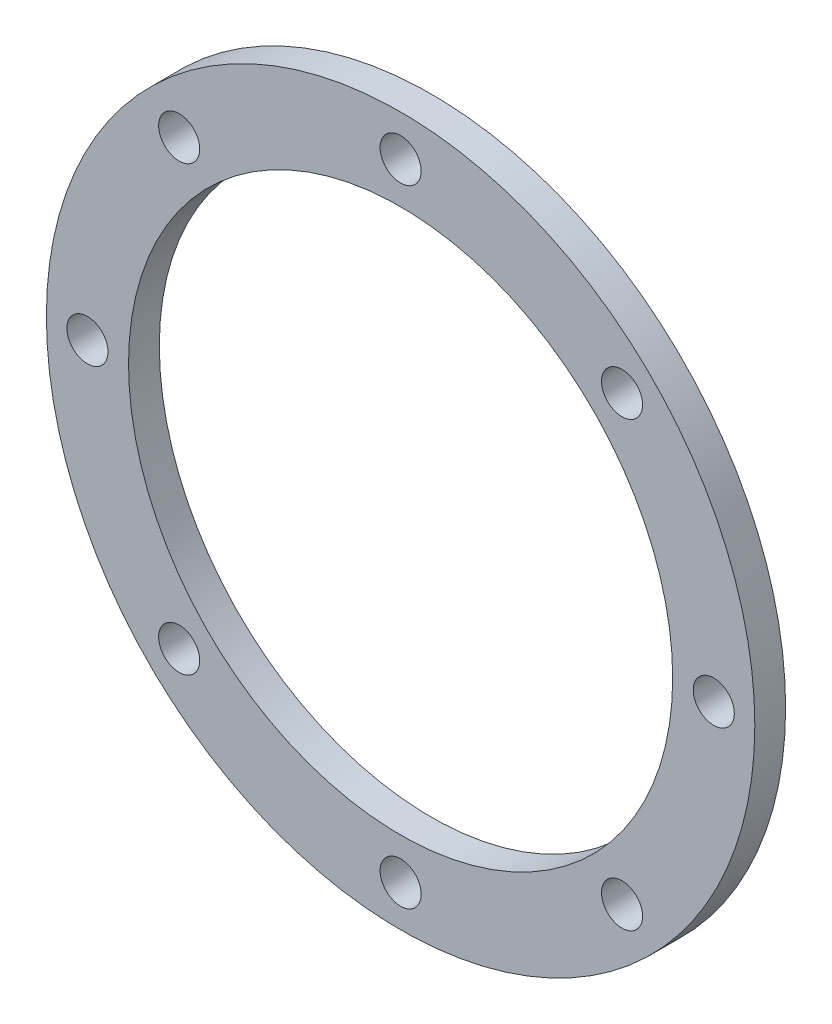
SolidWorks part; units mm, degrees
ref_plane "Front Plane" through (0, 0, 0) normal (0, 0, 1) x (1, 0, 0)
ref_plane "Top Plane" through (0, 0, 0) normal (0, 1, 0) x (1, 0, 0)
ref_plane "Right Plane" through (0, 0, 0) normal (1, 0, 0) x (0, 0, -1)
sketch "Sketch1" plane through (0, 0, 0) normal (0, 0, 1) x (1, 0, 0)
  circle A0 centre (0, 0) radius 84.1375
  circle A1 centre (0, 0) radius 109.5375
  dimension "D1" = 168.275
  dimension "D2" = 219.075
extrude "Extrude1" add sketch "Sketch1" along normal blind 9.525
hole_wizard "1/2 (0.5) Diameter Hole3" positions "3DSketch1" profile "Sketch2" hole size "1/2" standard "Ansi Inch"
sketch3d "3DSketch1"
  line L10 (0, 109.5375, 9.525) -> (0, 0, 9.525) construction
  circle A2 centre (0, 0, 9.525) radius 109.5375 construction
  circle A3 centre (0, 0, 9.525) radius 109.5375 construction
  point P5 (0, 96.8375, 9.525)
  point P24 (0, 0, 119.0625)
  point P26 (0, 0, 119.0625)
  dimension "D1" = 12.7
sketch "Sketch2" plane through (0, 96.8375, 9.525) normal (1, 0, 0) x (0, -1, 0)
  line L0 (0, 0) -> (0, 29.2155)
  line L1 (0, 29.2155) -> (6.35, 25.4)
  line L2 (6.35, 25.4) -> (6.35, 0)
  line L5 (6.35, 0) -> (0, 0)
  line L10 (0, 29.2155) -> (-6.35, 25.4) construction
  line L11 (0, -6.35) -> (0, 107.95) construction
  dimension "Hole Dia." = 12.7
  dimension "Hole Depth" = 25.4
  dimension "Drill Angle" = 118
pattern_circular "CirPattern1" [suppressed] count 6 over 360
pattern_circular "CirPattern2" count 8 over 360 about axis through (0, 0, 9.525) along (0, 0, -1) of "1/2 (0.5) Diameter Hole3"
equation "\"D2@Sketch1\" = \"D1@Sketch1\" + 2"
